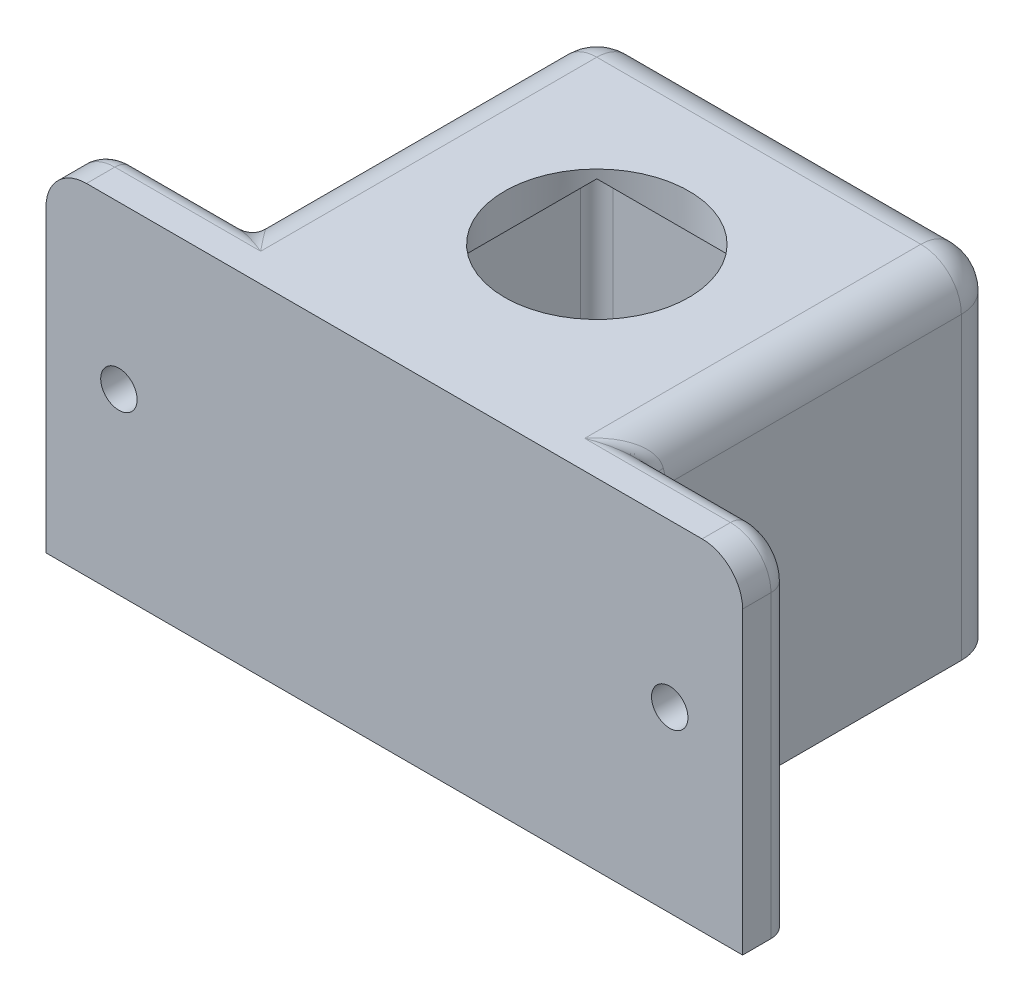
SolidWorks part; units mm, degrees
other "Stop Button Holder"
other "Interior Volume"
ref_plane "Front Plane" through (0, 0, 0) normal (0, 0, 1) x (1, 0, 0)
ref_plane "Top Plane" through (0, 0, 0) normal (0, 1, 0) x (1, 0, 0)
ref_plane "Right Plane" through (0, 0, 0) normal (1, 0, 0) x (0, 0, -1)
sketch "Half Body Sketch" plane through (0, 0, 0) normal (0, 1, 0) x (1, 0, 0)
  line L0 (0, 0) -> (0, 60.4502) construction
  line L1 (0, 50) -> (25, 50)
  line L2 (25, 50) -> (25, 6)
  line L3 (25, 6) -> (43, 6)
  line L4 (43, 6) -> (43, 0)
  line L5 (43, 0) -> (0, 0)
  line L6 (0, 50) -> (0, 0)
  dimension "D1" = 50
  dimension "D2" = 50
  dimension "D3" = 86
  dimension "D4" = 6
extrude "Half Body Extrude" add sketch "Half Body Sketch" along normal blind 42
mirror "Body Mirror" about plane through (0, 42, -50) normal (1, 0, 0) of bodies 101
fillet "Face Fillets" radius 5 5 edges at (-25, 42, -28) (-25, 21, -50) (25, 21, -50) (0, 42, -50) (25, 42, -28)
fillet "Corner Fillets" radius 5 2 edges at (43, 42, -3) (-43, 42, -3)
fillet "Wing Fillets" radius 2.5 6 edges at (-29, 42, -6) (-41.5355, 40.5355, -6) (29, 42, -6) (41.5355, 40.5355, -6) (-43, 18.5, -6) (43, 18.5, -6)
fillet "Transition Fillets" radius 2.5 6 edges at (22.4652, 41.35, -5.1815) (24.8296, 38.2941, -6) (-22.4652, 41.35, -5.1815) (-24.8296, 38.2941, -6) (25, 18.5, -6) (-25, 18.5, -6)
sketch "Interior Volume Sketch" plane through (0, 0, 0) normal (0, -1, 0) x (1, 0, 0)
  line L0 (25, -8.5) -> (25, -45) construction
  line L5 (-22, -3) -> (22, -3)
  line L6 (-22, -3) -> (-22, -47)
  line L7 (-22, -47) -> (22, -47)
  line L8 (22, -3) -> (22, -47)
  line L9 (20, -50) -> (-20, -50) construction
  line L10 (-25, -8.5) -> (-25, -45) construction
  line L11 (-43, 0) -> (43, 0) construction
  dimension "D1" = 3
  dimension "D2" = 3
  dimension "D3" = 3
  dimension "D4" = 3
extrude "Interior Volume Extrude" add sketch "Interior Volume Sketch" against normal offset from surface (38 mm away) 1 from offset 3 separate body up to face at (0, 42, -13) offset against normal yes
chamfer "Interior Volume Chamfer" distance 14 angle 45 4 edges at (22, 41, -25) (0, 41, -47) (0, 41, -3) (-22, 41, -25)
fillet "Interior Volume Fillet" radius 2 4 edges at (-22, 15, -47) (22, 15, -47) (-22, 15, -3) (22, 15, -3)
combine bodies "Cut Interior From Body" operation type subtract main body 102 bodies to subtract 103
sketch "Button Hole Sketch" plane through (0, 42, 0) normal (0, 1, 0) x (1, 0, 0)
  line L0 (-38, 0) -> (38, 0) construction
  circle A0 centre (0, 25) radius 11.375
  dimension "D1" = 22.75
  dimension "D2" = 25
extrude "Button Hole Cut Out" cut sketch "Button Hole Sketch" against normal up to next
sketch "Nut Access Sketch" plane through (0, 0, 0) normal (0, -1, 0) x (1, 0, 0)
  line L1 (0, -9.9889) -> (-13, -17.4944)
  line L2 (-13, -17.4944) -> (-13, -32.5056)
  line L3 (-13, -32.5056) -> (0, -40.0111)
  line L4 (0, -40.0111) -> (13, -32.5056)
  line L5 (13, -32.5056) -> (13, -17.4944)
  line L6 (13, -17.4944) -> (0, -9.9889)
  circle A0 centre (0, -25) radius 13 construction
  dimension "D1" = 26
extrude "Nut Access Cut Out" cut sketch "Nut Access Sketch" against normal blind 37.6
sketch "Mounting Screws Position Sketch" plane through (0, 0, -6) normal (0, 0, -1) x (-1, 0, 0)
  line L0 (0, 0) -> (0, 47.5161) construction
  line L1 (40.5, 0) -> (27.5, 0) construction
  point P0 (-34, 22)
  point P1 (34, 22)
  dimension "D1" = 68
  dimension "D2" = 22
hole_wizard "No. 6 Mounting Screws" [suppressed] positions "SketchNo. 6 Mounting Position Screws" profile "No. 6 Mounting Screws Profile Sketch" countersink size "#6" standard "ANSI Inch"
sketch "SketchNo. 6 Mounting Position Screws" plane through (0, 0, -6) normal (0, 0, -1) x (-1, 0, 0)
  point P0 (-34, 22)
  point P2 (34, 22)
sketch "No. 6 Mounting Screws Profile Sketch" plane through (34, 22, -6) normal (1, 0, 0) x (0, 1, 0)
  line L0 (0, 0) -> (0, 6)
  line L1 (0, 6) -> (1.8986, 6)
  line L2 (1.8986, 6) -> (1.8986, 1.892)
  line L3 (1.8986, 1.892) -> (3.5433, 0)
  line L5 (3.5433, 0) -> (0, 0)
  line L6 (-1.8986, 1.892) -> (-3.5433, 0) construction
  line L11 (0, -6.35) -> (0, 107.95) construction
  dimension "Thru Hole Dia." = 3.7973
  dimension "Thru Hole Depth" = 6
  dimension "Near C'Sink Dia." = 7.0866
  dimension "Near C'Sink Angle" = 82
hole_wizard "M4 Mounting Screws" positions "M4 Mounting Screws Position Sketch" profile "M4 Mounting ScrewsProfile Sketch" countersink size "M4" standard "ANSI Metric" end condition up to next
sketch3d "M4 Mounting Screws Position Sketch"
  point P0 (34, 22, -6)
  point P3 (-34, 22, -6)
sketch "M4 Mounting ScrewsProfile Sketch" plane through (34, 22, -6) normal (1, 0, 0) x (0, 1, 0)
  line L0 (0, 0) -> (0, 6)
  line L1 (0, 6) -> (2.25, 6)
  line L2 (2.25, 6) -> (2.25, 2.45)
  line L3 (2.25, 2.45) -> (4.7, 0)
  line L5 (4.7, 0) -> (0, 0)
  line L6 (-2.25, 2.45) -> (-4.7, 0) construction
  line L11 (0, -6.35) -> (0, 107.95) construction
  dimension "Thru Hole Dia." = 4.5
  dimension "Thru Hole Depth" = 6
  dimension "Near C'Sink Dia." = 9.4
  dimension "Near C'Sink Angle" = 90
